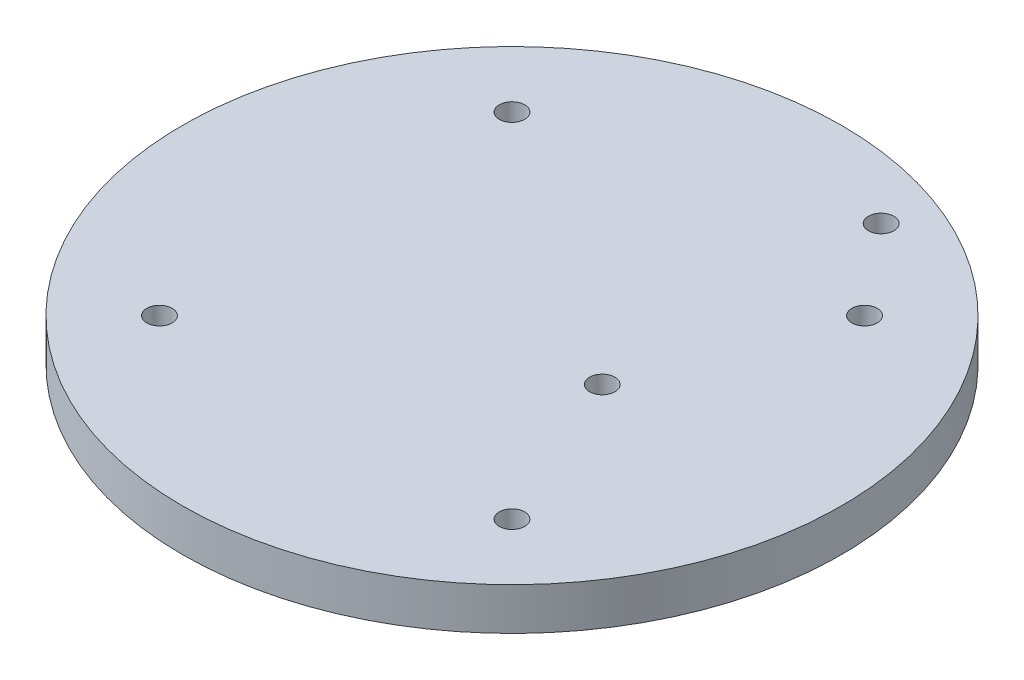
SolidWorks part; units mm, degrees
ref_plane "Plan de face" through (0, 0, 0) normal (0, 0, 1) x (1, 0, 0)
ref_plane "Plan de dessus" through (0, 0, 0) normal (0, 1, 0) x (1, 0, 0)
ref_plane "Plan de droite" through (0, 0, 0) normal (1, 0, 0) x (0, 0, -1)
sketch "Esquisse1" plane through (0, 0, 0) normal (0, 1, 0) x (1, 0, 0)
  circle A0 centre (0, 0) radius 39
  arc A1 (0, -39) -> (39, 0) centre (0, 0) ccw construction
extrude "Boss.-Extru.1" add sketch "Esquisse1" along normal blind 5
sketch "Esquisse2" plane through (0, 0, 0) normal (0, -1, 0) x (1, 0, 0)
  circle A0 centre (20.8597, 20.8597) radius 1.5
  circle A1 centre (20.8597, -20.8597) radius 1.5
  circle A2 centre (-20.8597, -20.8597) radius 1.5
  circle A3 centre (-20.8597, 20.8597) radius 1.5
  circle A4 centre (12.4, -31.2829) radius 1.5
  circle A5 centre (12.4, 1.7171) radius 1.5
  circle A6 centre (12.4, 1.7171) radius 1.25 construction
  circle A7 centre (12.4, -31.2829) radius 1.25 construction
  dimension "D1" = 3
extrude "Enlèv. mat.-Extru.1" cut sketch "Esquisse2" against normal through all
